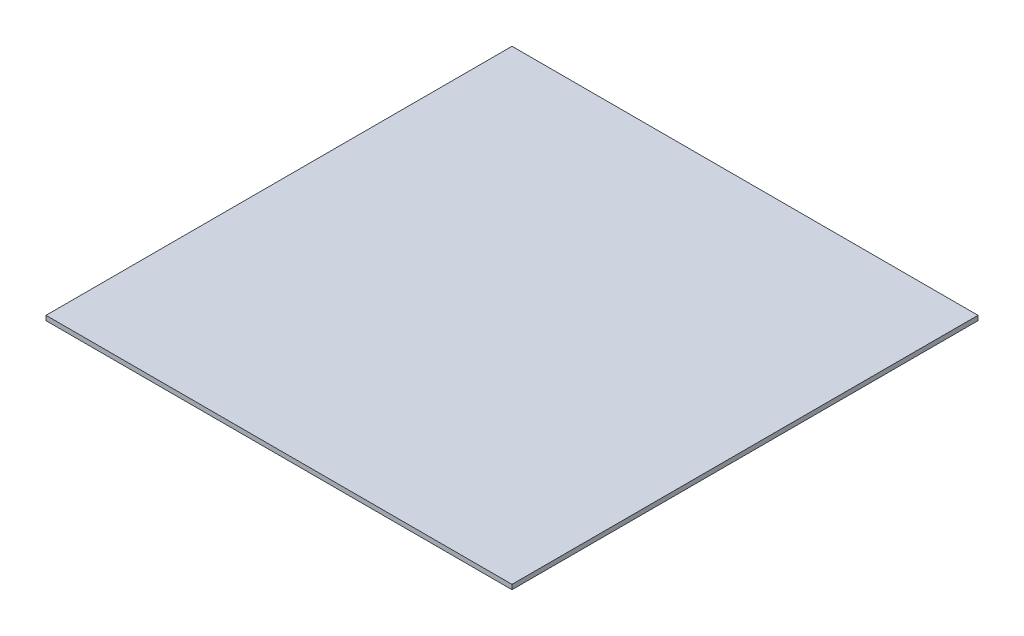
SolidWorks part; units mm, degrees
other "PCB"
ref_plane "Front Plane" through (0, 0, 0) normal (0, 0, 1) x (1, 0, 0)
ref_plane "Top Plane" through (0, 0, 0) normal (0, 1, 0) x (1, 0, 0)
ref_plane "Right Plane" through (0, 0, 0) normal (1, 0, 0) x (0, 0, -1)
sketch "Sketch1" plane through (0, 0, 0) normal (0, 1, 0) x (1, 0, 0)
  line L1 (-100, -100) -> (100, -100)
  line L2 (-100, -100) -> (-100, 100)
  line L3 (-100, 100) -> (100, 100)
  line L4 (100, -100) -> (100, 100)
  line L5 (-100, -100) -> (100, 100) construction
  line L6 (-100, 100) -> (100, -100) construction
  point P0 (0, 0)
  dimension "D1" = 200
extrude "Boss-Extrude1" add sketch "Sketch1" along normal blind 2
